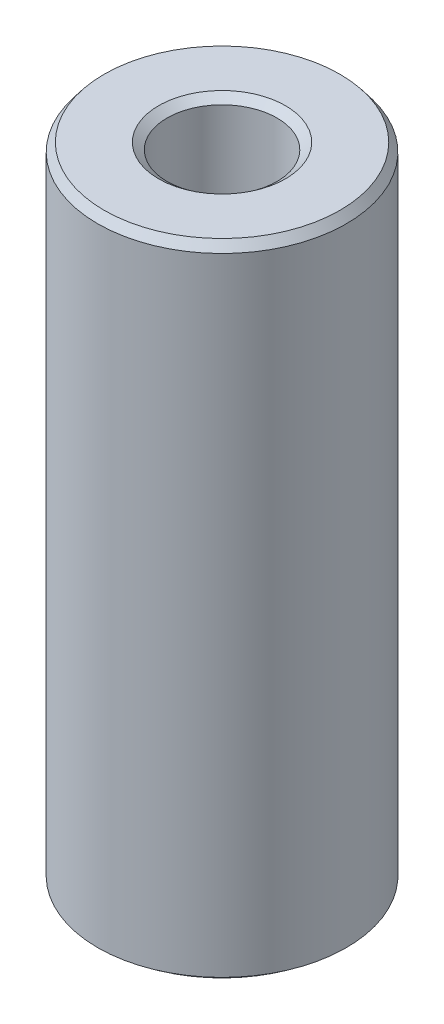
SolidWorks part; units mm, degrees
ref_plane "Front Plane" through (0, 0, 0) normal (0, 0, 1) x (1, 0, 0)
ref_plane "Top Plane" through (0, 0, 0) normal (0, 1, 0) x (1, 0, 0)
ref_plane "Right Plane" through (0, 0, 0) normal (1, 0, 0) x (0, 0, -1)
sketch "Sketch1" plane through (0, 0, 0) normal (0, 1, 0) x (1, 0, 0)
  circle A0 centre (0, 0) radius 32.5
  dimension "SLEEVE_OD" = 65
extrude "Boss-Extrude1" add sketch "Sketch1" along normal blind 167.7452
sketch "Sketch2" plane through (0, 0, 0) normal (0, 1, 0) x (1, 0, 0)
  circle A0 centre (0, 0) radius 14.377
  dimension "BORE_D" = 28.754
extrude "Cut-Extrude1" cut sketch "Sketch2" along normal through all
chamfer "Chamfer1" distance 2.2018 angle 37.416 4 edges at (0, 167.7452, 14.377) (0, 0, 14.377) (0, 0, 32.5) (0, 167.7452, 32.5) first distance on face at (0, 167.7452, 14.377) first distance on face at (0, 0, 14.377) first distance on face at (0, 167.7452, 32.5)
